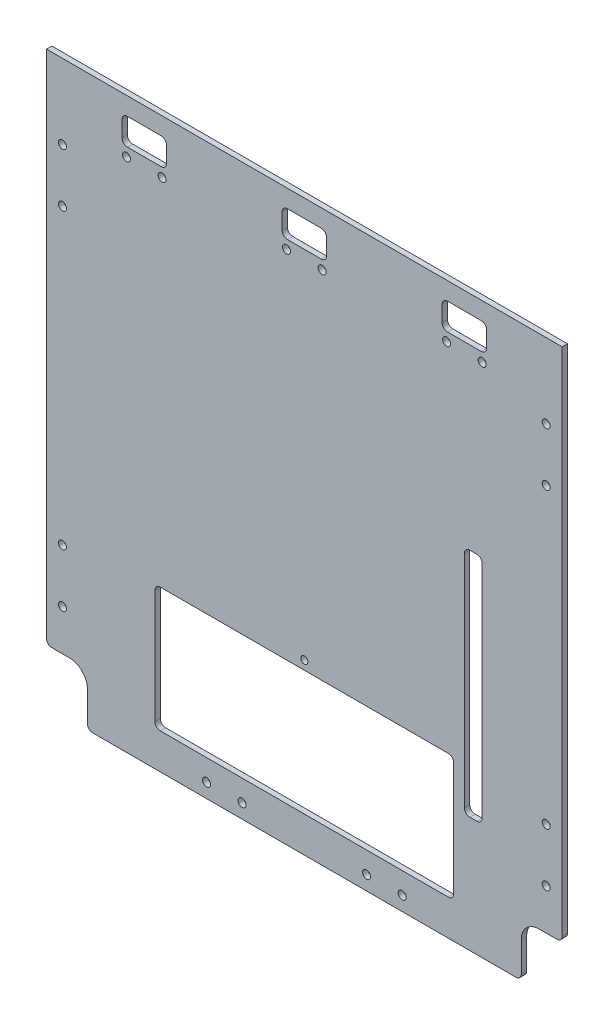
SolidWorks part; units mm, degrees
ref_plane "Front" through (0, 0, 0) normal (0, 0, 1) x (1, 0, 0)
ref_plane "Top" through (0, 0, 0) normal (0, 1, 0) x (1, 0, 0)
ref_plane "Right" through (0, 0, 0) normal (1, 0, 0) x (0, 0, -1)
sketch "Esquisse1" plane through (0, 0, 0) normal (0, 0, 1) x (1, 0, 0)
  line L1 (0, 0) -> (290, 0)
  line L2 (0, 0) -> (0, 320)
  line L3 (0, 320) -> (290, 320)
  line L4 (290, 0) -> (290, 320)
  dimension "D1" = 290
  dimension "D2" = 320
extrude "Boss.-Extru.1" add sketch "Esquisse1" along normal blind 3
sketch "Esquisse2" plane through (0, 0, 3) normal (0, 0, 1) x (1, 0, 0)
  line L0 (145, 0) -> (145, 172.6222) construction
  line L1 (290, 0) -> (267, 0)
  line L2 (290, 0) -> (290, 30)
  line L3 (290, 30) -> (267, 30)
  line L4 (267, 0) -> (267, 30)
  line L5 (0, 0) -> (290, 0) construction
  line L6 (23, 0) -> (23, 30)
  line L7 (0, 30) -> (23, 30)
  line L8 (0, 0) -> (0, 30)
  line L9 (0, 0) -> (23, 0)
  dimension "D1" = 23
  dimension "D2" = 30
extrude "Enlèv. mat.-Extru.1" cut sketch "Esquisse2" against normal through all both and the other way through all
fillet "Congé1" radius 10 2 edges at (23, 30, 1.5) (267, 30, 1.5)
fillet "Congé2" radius 3 4 edges at (267, 0, 1.5) (290, 30, 1.5) (23, 0, 1.5) (0, 30, 1.5)
sketch "Esquisse3" plane through (0, 0, 3) normal (0, 0, 1) x (1, 0, 0)
  line L0 (26, 0) -> (264, 0) construction
  line L1 (235, 195) -> (245, 195)
  line L2 (235, 195) -> (235, 65)
  line L3 (235, 65) -> (245, 65)
  line L4 (245, 195) -> (245, 65)
  dimension "D1" = 10
  dimension "D2" = 235
  dimension "D3" = 65
  dimension "D4" = 130
extrude "Enlèv. mat.-Extru.2" cut sketch "Esquisse3" against normal through all both and the other way through all
sketch "Esquisse4" plane through (0, 0, 3) normal (0, 0, 1) x (1, 0, 0)
  line L0 (26, 0) -> (264, 0) construction
  line L1 (61, 20) -> (229, 20)
  line L2 (61, 20) -> (61, 90)
  line L3 (61, 90) -> (229, 90)
  line L4 (229, 20) -> (229, 90)
  line L5 (145, 20) -> (145, 0) construction
  dimension "D1" = 70
  dimension "D2" = 20
  dimension "D3" = 168
extrude "Enlèv. mat.-Extru.3" cut sketch "Esquisse4" against normal through all both and the other way through all
fillet "Congé3" radius 3 8 edges at (235, 195, 1.5) (245, 195, 1.5) (245, 65, 1.5) (235, 65, 1.5) (229, 20, 1.5) (229, 90, 1.5) (61, 90, 1.5) (61, 20, 1.5)
sketch "Esquisse5" plane through (0, 0, 3) normal (0, 0, 1) x (1, 0, 0)
  line L0 (145, 0) -> (145, 95) construction
  line L1 (26, 0) -> (264, 0) construction
  line L2 (145, 8) -> (90, 8) construction
  circle A0 centre (145, 95) radius 2
  circle A1 centre (90, 8) radius 2.25
  circle A2 centre (110, 8) radius 2.25
  circle A3 centre (180, 8) radius 2.25
  circle A4 centre (200, 8) radius 2.25
  dimension "D1" = 4
  dimension "D3" = 110
  dimension "D4" = 4.5
  dimension "D6" = 20
  dimension "D2" = 95
  dimension "D5" = 8
extrude "Enlèv. mat.-Extru.4" cut sketch "Esquisse5" against normal through all both and the other way through all
sketch "Esquisse6" plane through (0, 0, 3) normal (0, 0, 1) x (1, 0, 0)
  line L0 (281, 308.1366) -> (281, -83.1051) construction
  line L1 (45, 290) -> (65, 290) construction
  line L2 (145, 0) -> (145, 67.282) construction
  line L3 (26, 0) -> (264, 0) construction
  line L4 (281, 165.5) -> (145, 165.5) construction
  line L5 (145, 320) -> (145, 263.6078) construction
  line L6 (290, 320) -> (0, 320) construction
  line L7 (245, 290) -> (225, 290) construction
  circle A0 centre (281, 83) radius 2.25
  circle A1 centre (281, 53) radius 2.25
  circle A2 centre (281, 278) radius 2.25
  circle A3 centre (281, 248) radius 2.25
  circle A4 centre (9, 248) radius 2.25
  circle A5 centre (9, 278) radius 2.25
  circle A6 centre (9, 53) radius 2.25
  circle A7 centre (9, 83) radius 2.25
  circle A8 centre (135, 290) radius 2.25
  circle A9 centre (155, 290) radius 2.25
  circle A10 centre (45, 290) radius 2.25
  circle A11 centre (65, 290) radius 2.25
  circle A12 centre (225, 290) radius 2.25
  circle A13 centre (245, 290) radius 2.25
  point P36 (55, 290)
  dimension "D2" = 4.5
  dimension "D3" = 30
  dimension "D4" = 53
  dimension "D5" = 195
  dimension "D8" = 20
  dimension "D1" = 136
  dimension "D6" = 20
  dimension "D7" = 30
  dimension "D9" = 90
  dimension "D10" = 30
extrude "Enlèv. mat.-Extru.5" cut sketch "Esquisse6" against normal through all both and the other way through all
sketch "Esquisse7" plane through (0, 0, 3) normal (0, 0, 1) x (1, 0, 0)
  line L0 (135, 290) -> (155, 290) construction
  line L1 (145, 290) -> (145, 310) construction
  line L2 (157.5, 310) -> (132.5, 310)
  line L3 (132.5, 310) -> (132.5, 295)
  line L4 (132.5, 295) -> (157.5, 295)
  line L5 (157.5, 310) -> (157.5, 295)
  line L6 (45, 290) -> (65, 290) construction
  line L7 (55, 290) -> (55, 310) construction
  line L8 (67.5, 310) -> (42.5, 310)
  line L9 (42.5, 310) -> (42.5, 295)
  line L10 (42.5, 295) -> (67.5, 295)
  line L11 (67.5, 310) -> (67.5, 295)
  line L12 (235, 290) -> (235, 310) construction
  line L13 (245, 290) -> (225, 290) construction
  line L14 (222.5, 310) -> (222.5, 295)
  line L15 (247.5, 295) -> (222.5, 295)
  line L16 (247.5, 310) -> (247.5, 295)
  line L17 (222.5, 310) -> (247.5, 310)
  point P10 (145, 295)
  point P21 (55, 295)
  point P30 (235, 295)
  dimension "D1" = 20
  dimension "D2" = 15
  dimension "D3" = 25
  dimension "D4" = 25
  dimension "D5" = 20
  dimension "D6" = 15
extrude "Enlèv. mat.-Extru.6" cut sketch "Esquisse7" against normal through all both and the other way through all
fillet "Congé4" radius 3 12 edges at (222.5, 295, 1.5) (247.5, 295, 1.5) (247.5, 310, 1.5) (222.5, 310, 1.5) (132.5, 310, 1.5) (157.5, 310, 1.5) (132.5, 295, 1.5) (157.5, 295, 1.5) (67.5, 295, 1.5) (67.5, 310, 1.5) (42.5, 310, 1.5) (42.5, 295, 1.5)
